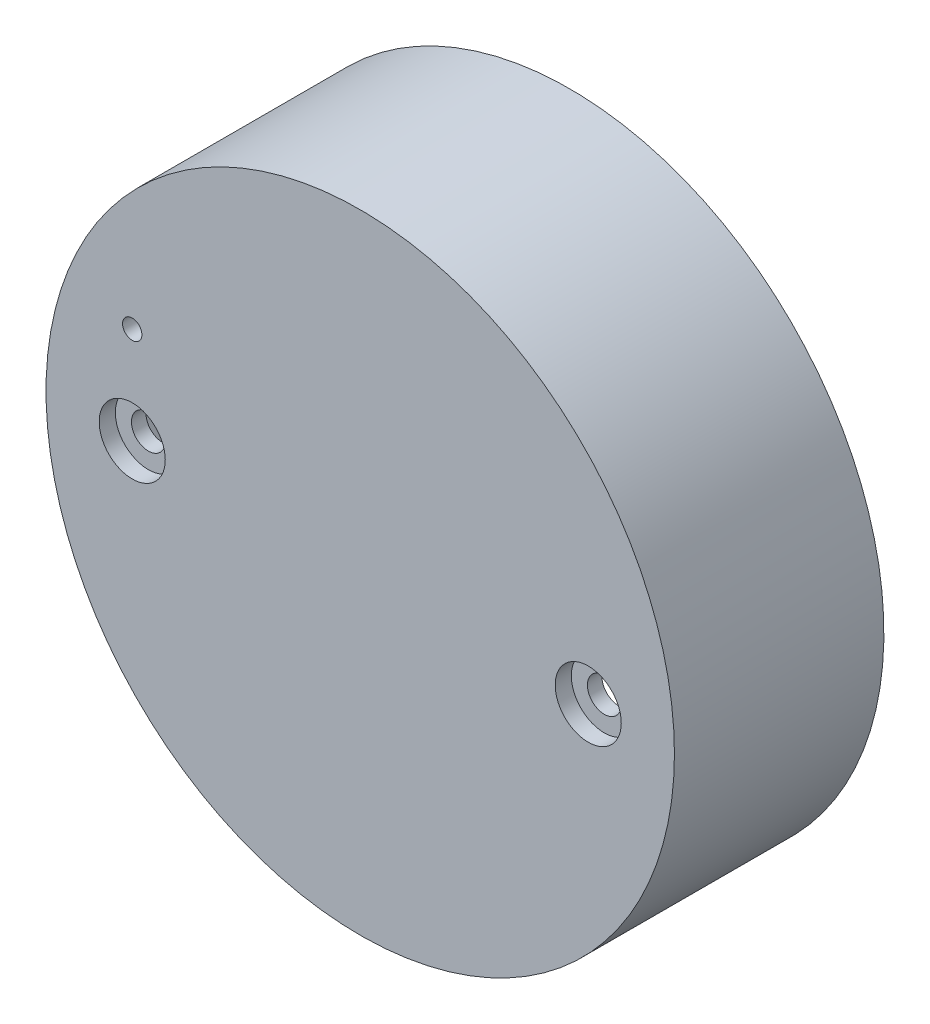
SolidWorks part; units mm, degrees
material "Thornel Mat VMA"
ref_plane "前视基准面" through (0, 0, 0) normal (0, 0, 1) x (1, 0, 0)
ref_plane "上视基准面" through (0, 0, 0) normal (0, 1, 0) x (1, 0, 0)
ref_plane "右视基准面" through (0, 0, 0) normal (1, 0, 0) x (0, 0, -1)
other "Configuration Table"
sketch "草图1" plane through (0, 0, 0) normal (0, 0, 1) x (1, 0, 0)
  line L0 (-4.9697, -5.3068) -> (15.3903, -5.3068) construction
  line L1 (-1.7897, -9.462) -> (12.2103, -9.462) construction
  line L2 (5.2103, 9.538) -> (5.2103, -5.6737) construction
  line L3 (5.2103, -5.6737) -> (5.2103, -9.462) construction
  line L4 (-20.5262, 27.538) -> (29.3458, 27.538) construction
  arc A1 (15.3903, -5.3068) -> (-4.9697, -5.3068) centre (5.2103, 9.538) ccw construction
  circle A2 centre (5.2103, 9.538) radius 18 construction
  circle A3 centre (5.2103, 9.538) radius 19.5 construction
  spline S0 degree 2 poles (-4.9697, -5.3068) (-1.8954, -6.8939) (-1.7897, -9.462) knots 0 0 0 0.933514 0.933514 0.933514 construction
  spline S1 degree 2 poles (15.3903, -5.3068) (12.316, -6.8939) (12.2103, -9.462) knots 0 0 0 0.933514 0.933514 0.933514 construction
  point P7 (5.2103, -9.462)
  dimension "D1" = 20.36
  dimension "D2" = 36
  dimension "D6" = 39
  dimension "D3" = 19
  dimension "D4" = 14
  dimension "D5" = 37
sketch "草图2" plane through (0, 0, 0) normal (0, 0, 1) x (1, 0, 0)
  circle A0 centre (5.2103, 9.538) radius 19.5
  circle A1 centre (5.2103, 9.538) radius 19.5 construction
extrude "凸台-拉伸1" add sketch "草图2" along normal blind 13
sketch "草图3" plane through (0, 0, 0) normal (0, 0, 1) x (1, 0, 0)
  arc A1 (-2.0895, -9.4744) -> (12.51, -9.4744) centre (5.2103, 9.538) ccw
  arc A2 (15.5443, -5.5649) -> (-5.1238, -5.5649) centre (5.2103, 9.538) ccw
  arc A3 (15.5443, -5.5649) -> (-5.1238, -5.5649) centre (5.2103, 9.538) ccw
  spline S0 degree 3 poles (229.8671, -2977.6257) (427.1916, -179.0998) (-8.4928, -35.7015) (35.8591, 22.0661) (561.3621, -75.3509) (2726.8544, -1276.7174) knots -21.363862 -21.363862 -21.363862 -21.363862 0.5 0.5 23.131712 23.131712 23.131712 23.131712 only from (12.51, -9.4744) to (15.5443, -5.5649)
  spline S1 degree 3 poles (-2716.4543, -1276.7288) (-550.9449, -75.3515) (-25.4386, 22.0662) (18.9132, -35.7012) (-416.7636, -179.0973) (-219.4516, -2977.5533) knots -22.131783 -22.131783 -22.131783 -22.131783 0.5 0.5 22.363674 22.363674 22.363674 22.363674 only from (-5.1238, -5.5649) to (-2.0895, -9.4744)
  spline S2 degree 3 poles (12.51, -9.4744) (12.5429, -8.6746) (12.8021, -7.9653) (13.7989, -6.667) (14.5427, -6.0797) (15.5443, -5.5649) knots 0 0 0 0 0.5 0.5 1 1 1 1
  spline S3 degree 3 poles (-5.1238, -5.5649) (-4.1222, -6.0797) (-3.3783, -6.667) (-2.3815, -7.9653) (-2.1224, -8.6746) (-2.0895, -9.4744) knots 0 0 0 0 0.5 0.5 1 1 1 1
  dimension "D1" = 0.3
extrude "切除-拉伸1" cut sketch "草图3" along normal blind 1.5
sketch "草图4" plane through (0, 0, 0) normal (0, 0, 1) x (1, 0, 0)
  circle A0 centre (5.2103, 9.538) radius 18.3
  arc A1 (15.5443, -5.5649) -> (-5.1238, -5.5649) centre (5.2103, 9.538) ccw construction
extrude "切除-拉伸2" cut sketch "草图4" along normal blind 11.1
sketch "草图5" plane through (0, 0, 0) normal (0, 0, 1) x (1, 0, 0)
  line L0 (15.2103, 22.538) -> (-4.7897, -3.462) construction
  line L1 (15.2103, 22.538) -> (-4.7897, 22.538) construction
  line L2 (15.2103, 22.538) -> (15.2103, -3.462) construction
  line L3 (15.2103, -3.462) -> (-4.7897, -3.462) construction
  line L4 (-4.7897, 22.538) -> (-4.7897, -3.462) construction
  line L5 (-4.7897, 22.538) -> (15.2103, -3.462) construction
  line L6 (15.2103, 9.538) -> (23.5103, 9.538) construction
  line L7 (-4.7897, 9.538) -> (-13.0897, 9.538) construction
  line L8 (-8.9397, 9.538) -> (-8.9397, 15.538) construction
  circle A0 centre (5.2103, 9.538) radius 18.3 construction
  circle A1 centre (19.3603, 9.538) radius 1.05
  circle A2 centre (-8.9397, 9.538) radius 1.05
  circle A3 centre (-8.9397, 15.538) radius 0.6
  point P4 (5.2103, 9.538)
  dimension "D3" = 2.1
  dimension "D4" = 2.1
  dimension "D6" = 1.2
  dimension "D1" = 20
  dimension "D2" = 26
  dimension "D5" = 6
extrude "切除-拉伸3" cut sketch "草图5" along normal through all
sketch "草图6" plane through (0, 0, 13) normal (0, 0, 1) x (1, 0, 0)
  circle A0 centre (-8.9397, 9.538) radius 2.05
  circle A1 centre (19.3603, 9.538) radius 2.05
  dimension "D1" = 4.1
extrude "切除-拉伸4" cut sketch "草图6" against normal blind 1
ref_plane "基准面1" through (0, 0, 3.1) normal (0, 0, -1) x (-1, 0, 0)
sketch "草图8" plane through (0, 0, 3.1) normal (0, 0, -1) x (-1, 0, 0)
  line L0 (-5.2103, 9.538) -> (-5.2103, -9.962) construction
  line L1 (-9.5853, -9.962) -> (-0.8353, -9.962)
  line L2 (-9.5853, -9.962) -> (-9.5853, -2.662)
  line L3 (-9.5853, -2.662) -> (-0.8353, -2.662)
  line L4 (-0.8353, -2.662) -> (-0.8353, -9.962)
  arc A0 (-12.6847, -8.4727) -> (2.2641, -8.4727) centre (-5.2103, 9.538) ccw construction
  point P8 (-5.2103, -9.962)
  dimension "D1" = 8.75
  dimension "D2" = 7.3
extrude "切除-拉伸5" cut sketch "草图8" against normal blind 3.25
